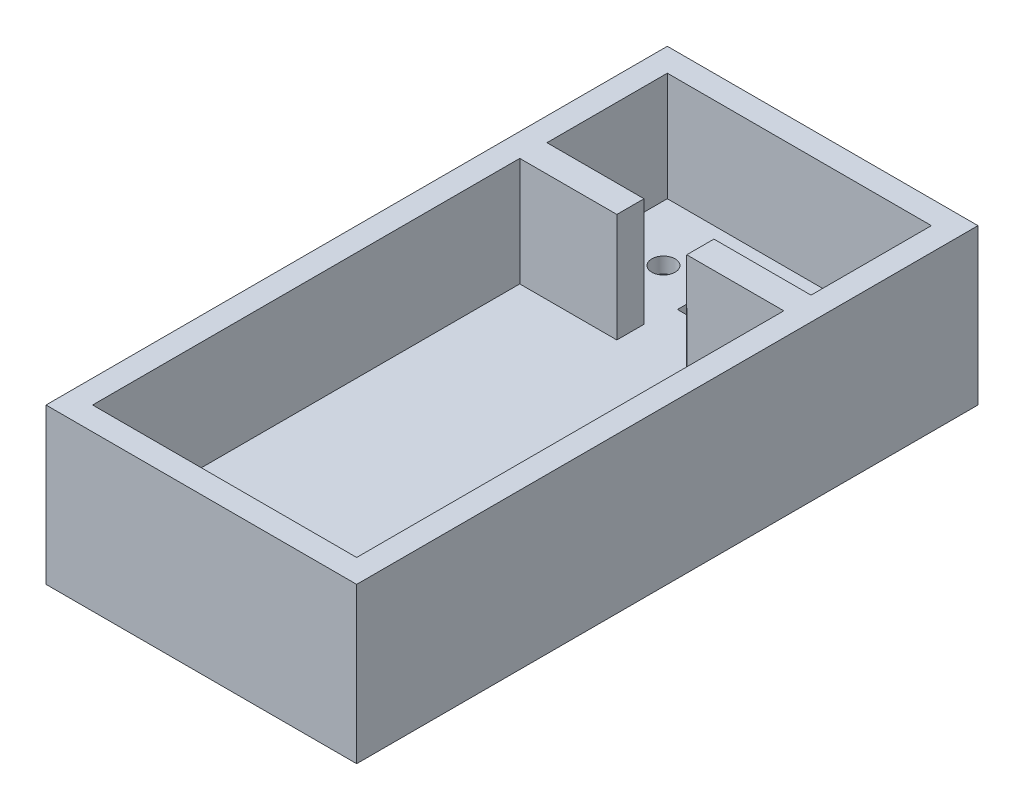
SolidWorks part; units mm, degrees
ref_plane "Front Plane" through (0, 0, 0) normal (0, 0, 1) x (1, 0, 0)
ref_plane "Top Plane" through (0, 0, 0) normal (0, 1, 0) x (1, 0, 0)
ref_plane "Right Plane" through (0, 0, 0) normal (1, 0, 0) x (0, 0, -1)
sketch "Sketch1" plane through (0, 0, 0) normal (0, 1, 0) x (1, 0, 0)
  line L0 (9.8005, 29.3006) -> (-9.8005, 29.3006) construction
  line L1 (-20, -40) -> (20, -40)
  line L2 (-20, -40) -> (-20, 40)
  line L3 (-20, 40) -> (20, 40)
  line L4 (20, -40) -> (20, 40)
  line L5 (0, 40) -> (0, -40) construction
  line L6 (-20, 0) -> (20, 0) construction
  line L7 (17, -37) -> (-17, -37)
  line L8 (17, -37) -> (17, 18)
  line L9 (17, 37) -> (-17, 37)
  line L10 (-17, -37) -> (-17, 18)
  line L11 (0, 37) -> (0, -37) construction
  line L12 (17, 0) -> (-17, 0) construction
  line L13 (0, 29.3006) -> (0, 27.3006) construction
  line L14 (-9.8005, 32.476) -> (-12.5505, 30.8883)
  line L15 (-12.5505, 30.8883) -> (-12.5505, 27.7129)
  line L16 (-12.5505, 27.7129) -> (-9.8005, 26.1252)
  line L17 (-9.8005, 26.1252) -> (-7.0505, 27.7129)
  line L18 (-7.0505, 27.7129) -> (-7.0505, 30.8883)
  line L19 (-7.0505, 30.8883) -> (-9.8005, 32.476)
  line L20 (9.8005, 32.476) -> (7.0505, 30.8883)
  line L21 (7.0505, 30.8883) -> (7.0505, 27.7129)
  line L22 (7.0505, 27.7129) -> (9.8005, 26.1252)
  line L23 (9.8005, 26.1252) -> (12.5505, 27.7129)
  line L24 (12.5505, 27.7129) -> (12.5505, 30.8883)
  line L25 (12.5505, 30.8883) -> (9.8005, 32.476)
  line L26 (0, -37) -> (0, 18) construction
  line L27 (-4, 25.3006) -> (4, 25.3006)
  line L28 (-4, 25.3006) -> (-4, 29.3006)
  line L29 (-4, 29.3006) -> (4, 29.3006)
  line L30 (4, 25.3006) -> (4, 29.3006)
  line L31 (0, 29.3006) -> (0, 25.3006) construction
  line L32 (-4, 27.3006) -> (4, 27.3006) construction
  line L33 (-4.5, 18) -> (4.5, 18) construction
  line L34 (-17, 21.5) -> (-17, 37)
  line L35 (-4.5, 18) -> (-17, 18)
  line L36 (-4.5, 18) -> (-4.5, 21.5)
  line L37 (-4.5, 21.5) -> (-17, 21.5)
  line L39 (4.5, 18) -> (17, 18)
  line L40 (4.5, 18) -> (4.5, 21.5)
  line L41 (4.5, 21.5) -> (17, 21.5)
  line L43 (17, 21.5) -> (17, 37)
  circle A0 centre (-9.8005, 29.3006) radius 1.5
  circle A1 centre (9.8005, 29.3006) radius 1.5
  circle A2 centre (-9.8005, 29.3006) radius 2.75 construction
  circle A3 centre (9.8005, 29.3006) radius 2.75 construction
  point P0 (0, 0)
  point P4 (0, 0)
  point P14 (0, 29.3006)
  point P45 (0, 18)
  dimension "D5" = 3
  dimension "D6" = 5.5
  dimension "D1" = 80
  dimension "D2" = 40
  dimension "D3" = 3
  dimension "D4" = 3
  dimension "D7" = 2
  dimension "D8" = 55
  dimension "D9" = 8
  dimension "D10" = 4.5
  dimension "D11" = 3.5
  dimension "D12" = 15.5
extrude "Initial Extrude" add sketch "Sketch1" along normal blind 20 contours L10 L7 L8 L9 | L1 L4 L3 L2 L7 L10 L9 L8 | L18 L19 L14 L15 L16 L17 A0 | L24 L25 L20 L21 L22 L23 A1 region at (-19.1056, 0, 0) region at (0, 0, 1.7648) region at (-8.4675, 0, -31.6094) region at (11.1335, 0, -31.6094)
extrude "Main Cavity" cut sketch "Sketch1<3>" along normal through all from offset 6 contours L10 L7 L8 L9 | L18 L19 L14 L15 L16 L17 A0 | L24 L25 L20 L21 L22 L23 A1 region at (0, 0, 1.7648) region at (-8.4675, 0, -31.6094) region at (11.1335, 0, -31.6094)
sketch "Sketch1<3>" plane through (0, 0, 0) normal (0, 1, 0) x (1, 0, 0) same geometry as "Sketch1"
extrude "Nut Capture Bottom" cut sketch "Sketch1<4>" along normal blind 4 contours L24 L25 L20 L21 L22 L23 A1 | L18 L19 L14 L15 L16 L17 A0 region at (-8.4675, 0, -31.6094) region at (11.1335, 0, -31.6094)
sketch "Sketch1<4>" plane through (0, 0, 0) normal (0, 1, 0) x (1, 0, 0) same geometry as "Sketch1"
chamfer "Sensor Hole Chamfer" distance 1 angle 45 4 edges at (0, 0, -25.3006) (-4, 0, -27.3006) (0, 0, -29.3006) (4, 0, -27.3006)
sketch "Sketch3" plane through (0, 6, 0) normal (0, 1, 0) x (1, 0, 0)
  line L0 (0, 37) -> (0, 33.5) construction
  line L1 (17, 37) -> (-17, 37) construction
  line L3 (-8, 32) -> (8, 32)
  line L4 (-8, 32) -> (-8, 35)
  line L5 (-8, 35) -> (8, 35)
  line L6 (8, 32) -> (8, 35)
  line L7 (0, 35) -> (0, 32) construction
  line L8 (-8, 33.5) -> (8, 33.5) construction
  dimension "D1" = 3.5
  dimension "D2" = 3
  dimension "D3" = 16
extrude "GPIO Cutout Sensor" cut sketch "Sketch3" against normal blind 3
